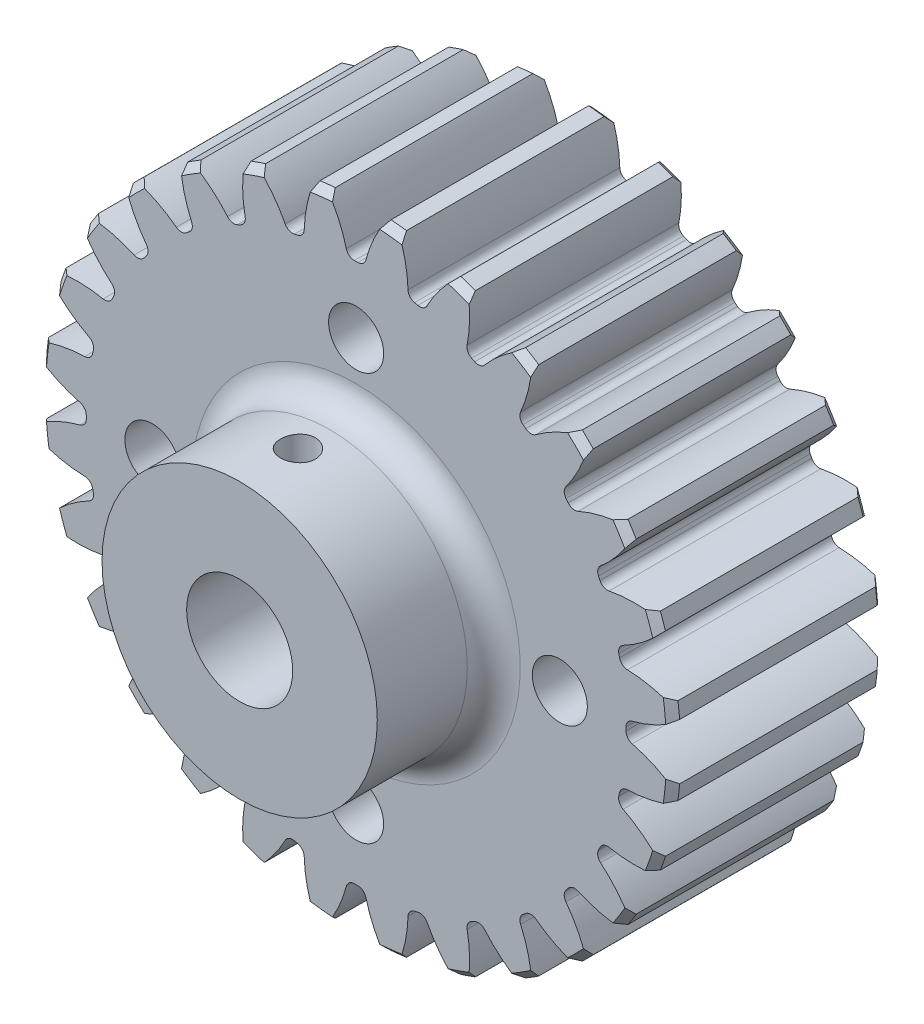
SolidWorks part; units mm, degrees
ref_plane "Front Plane" through (0, 0, 0) normal (0, 0, 1) x (1, 0, 0)
ref_plane "Top Plane" through (0, 0, 0) normal (0, 1, 0) x (1, 0, 0)
ref_plane "Right Plane" through (0, 0, 0) normal (1, 0, 0) x (0, 0, -1)
sketch "Sketch1" plane through (0, 0, 0) normal (0, 0, 1) x (1, 0, 0)
  line L0 (0, 0) -> (0, 28) construction
  line L1 (-8.999, 31.2754) -> (8.999, 24.7246) construction
  circle A0 centre (0, 0) radius 25.5 construction
  circle A1 centre (0, 0) radius 30 construction
  circle A2 centre (0, 0) radius 28 construction
  circle A3 centre (0, 0) radius 26.3114 construction
  circle A4 centre (0, 0) radius 22.5 construction
  circle A5 centre (0, 0) radius 6 construction
  point P8 (1, 0)
  point P13 (14, 0)
  dimension "OD" = 60
  dimension "Root Diameter" = 51
  dimension "Gear Pitch Diameter" = 56
  dimension "Base Diameter" = 52.6228
  dimension "Hub Diameter" = 45
  dimension "For Shaft Diameter" = 12
  dimension "Pressure Angle" = 20
  dimension "Number of Teeth" = 28
  dimension "Module" = 2
sketch "Sketch2" plane through (0, 0, 0) normal (1, 0, 0) x (0, 0, -1)
  line L0 (-16, 0) -> (20, 0) construction
  line L1 (20, 30) -> (20, -30) construction
  line L2 (0, -22.5) -> (-16, -22.5) construction
  line L3 (-16, 30) -> (20, 30) construction
  line L8 (-16, -22.5) -> (-16, 22.5) construction
  point P4 (0, 30)
  point P5 (-8, 0)
  dimension "Overall Width" = 36
  dimension "Hub Width" = 16
  dimension "Approx Set Screw Positon" = 8
  dimension "Face Width" = 20
sketch "Sketch3" plane through (0, 0, 0) normal (0, 0, 1) x (1, 0, 0)
  circle A0 centre (0, 0) radius 30
  circle A1 centre (0, 0) radius 30 construction
extrude "Boss-Extrude1" add sketch "Sketch3" against normal up to vertex (20 mm away) and the other way up to vertex (16 mm away) up to point (0, 0, -20) other way up to point (0, 0, 16)
sketch "Sketch5" plane through (0, 0, 0) normal (1, 0, 0) x (0, 0, -1)
  line L1 (0, 22.5) -> (-16, 22.5)
  line L2 (0, 22.5) -> (0, 30)
  line L3 (0, 30) -> (-16, 30)
  line L4 (-16, 22.5) -> (-16, 30)
  line L5 (-16, 0) -> (20, 0)
  line L6 (-16, 0) -> (-16, 6)
  line L7 (-16, 6) -> (20, 6)
  line L8 (20, 0) -> (20, 6)
  point P5 (0, 22.5)
  point P12 (0, 6)
revolve "Cut-Revolve1" cut sketch "Sketch5" angle 360 about L0
fillet "Fillet2" radius 0.671 1 edges at (0, -22.5, 0)
chamfer "Chamfer1" distance 0.671 angle 45 5 edges at (0, -6, -20) (0, -30, 0) (30, 0, -20) (0, -6, 16) (0, -22.5, 16)
sketch "Sketch4" plane through (0, 0, 0) normal (0, 0, 1) x (1, 0, 0)
  line L0 (25.4879, 0.7854) -> (25.4879, -0.7854)
  arc A3 (29.8844, 2.6316) -> (29.8844, -2.6316) centre (0, 0) cw
  circle A4 centre (0, 0) radius 30 construction
  arc A5 (25.4879, 0.7854) -> (29.8844, 2.6316) centre (22.9219, 13.0538) ccw
  circle A8 centre (0, 0) radius 25.5 construction
  arc A9 (25.4879, -0.7854) -> (29.8844, -2.6316) centre (22.9219, -13.0538) cw
  spline S0 degree 4 poles (26.2891, 1.0836) (26.2949, 1.0839) (26.3112, 1.085) (26.3421, 1.0878) (26.3923, 1.0937) (26.4563, 1.1028) (26.5387, 1.1166) (26.6357, 1.1354) (26.7419, 1.1588) (26.8572, 1.187) (26.972, 1.2177) (27.0862, 1.2508) (27.1997, 1.2858) (27.3368, 1.3307) (27.5008, 1.388) (27.6916, 1.4601) (27.9071, 1.5478) (28.1257, 1.6435) (28.3399, 1.743) (28.5551, 1.8495) (28.7626, 1.9568) (28.9769, 2.0743) (29.174, 2.1859) (29.3935, 2.3177) (29.5702, 2.426) (29.8016, 2.5761) (29.9378, 2.6669) (30.0966, 2.7755) (30.1668, 2.8251) (30.2101, 2.8556) knots 0 0 0 0 0 0.005377 0.015084 0.028532 0.04661 0.064855 0.092111 0.119476 0.146842 0.174209 0.201575 0.228941 0.256307 0.307035 0.361767 0.4165 0.471232 0.525964 0.580697 0.635429 0.690161 0.744894 0.799626 0.854358 0.909091 0.954545 1 1 1 1 1 construction
  spline S1 degree 4 poles (26.2891, 1.0836) (26.2949, 1.0839) (26.3112, 1.085) (26.3421, 1.0878) (26.3923, 1.0937) (26.4563, 1.1028) (26.5387, 1.1166) (26.6357, 1.1354) (26.7419, 1.1588) (26.8572, 1.187) (26.972, 1.2177) (27.0862, 1.2508) (27.1997, 1.2858) (27.3368, 1.3307) (27.5008, 1.388) (27.6916, 1.4601) (27.9071, 1.5478) (28.1257, 1.6435) (28.3399, 1.743) (28.5551, 1.8495) (28.7626, 1.9568) (28.9769, 2.0743) (29.174, 2.1859) (29.3935, 2.3177) (29.5702, 2.426) (29.7514, 2.5436) (29.8394, 2.6016) (29.8844, 2.6316) knots 0 0 0 0 0 0.005377 0.015084 0.028532 0.04661 0.064855 0.092111 0.119476 0.146842 0.174209 0.201575 0.228941 0.256307 0.307035 0.361767 0.4165 0.471232 0.525964 0.580697 0.635429 0.690161 0.744894 0.799626 0.854358 0.909091 0.909091 0.909091 0.909091 0.909091 construction
  spline S2 degree 4 poles (26.2891, -1.0836) (26.2949, -1.0839) (26.3112, -1.085) (26.3421, -1.0878) (26.3923, -1.0937) (26.4563, -1.1028) (26.5387, -1.1166) (26.6357, -1.1354) (26.7419, -1.1588) (26.8572, -1.187) (26.972, -1.2177) (27.0862, -1.2508) (27.1997, -1.2858) (27.3368, -1.3307) (27.5008, -1.388) (27.6916, -1.4601) (27.9071, -1.5478) (28.1257, -1.6435) (28.3399, -1.743) (28.5551, -1.8495) (28.7626, -1.9568) (28.9769, -2.0743) (29.174, -2.1859) (29.3935, -2.3177) (29.5702, -2.426) (29.8016, -2.5761) (29.9378, -2.6669) (30.0966, -2.7755) (30.1668, -2.8251) (30.2101, -2.8556) knots 0 0 0 0 0 0.005377 0.015084 0.028532 0.04661 0.064855 0.092111 0.119476 0.146842 0.174209 0.201575 0.228941 0.256307 0.307035 0.361767 0.4165 0.471232 0.525964 0.580697 0.635429 0.690161 0.744894 0.799626 0.854358 0.909091 0.954545 1 1 1 1 1 construction
  spline S3 degree 4 poles (26.2891, -1.0836) (26.2949, -1.0839) (26.3112, -1.085) (26.3421, -1.0878) (26.3923, -1.0937) (26.4563, -1.1028) (26.5387, -1.1166) (26.6357, -1.1354) (26.7419, -1.1588) (26.8572, -1.187) (26.972, -1.2177) (27.0862, -1.2508) (27.1997, -1.2858) (27.3368, -1.3307) (27.5008, -1.388) (27.6916, -1.4601) (27.9071, -1.5478) (28.1257, -1.6435) (28.3399, -1.743) (28.5551, -1.8495) (28.7626, -1.9568) (28.9769, -2.0743) (29.174, -2.1859) (29.3935, -2.3177) (29.5702, -2.426) (29.7514, -2.5436) (29.8394, -2.6016) (29.8844, -2.6316) knots 0 0 0 0 0 0.005377 0.015084 0.028532 0.04661 0.064855 0.092111 0.119476 0.146842 0.174209 0.201575 0.228941 0.256307 0.307035 0.361767 0.4165 0.471232 0.525964 0.580697 0.635429 0.690161 0.744894 0.799626 0.854358 0.909091 0.909091 0.909091 0.909091 0.909091 construction
  dimension "D1" = 1.5708
extrude "Cut-Extrude1" cut sketch "Sketch4" against normal through all both and the other way through all
fillet "Fillet1" radius 0.7854 2 edges at (25.4879, 0.7854, -10) (25.4879, -0.7854, -10)
pattern_circular "CirPattern1" count 28 over 360 about axis through (0, 0, 16) along (0, 0, -1) of "Cut-Extrude1", "Fillet1"
sketch "Sketch6" plane through (0, 0, -20) normal (0, 0, -1) x (-1, 0, 0)
  circle A0 centre (0, 0) radius 6.671
  circle A1 centre (0, 0) radius 5.0075
  circle A2 centre (0, 0) radius 6.671 construction
  dimension "D1" = 10.015
extrude "Boss-Extrude2" add sketch "Sketch6" against normal through all
sketch "Sketch7" plane through (0, 0, 16) normal (0, 0, 1) x (1, 0, 0)
  circle A0 centre (0, 0) radius 23.171
  circle A2 centre (0, 0) radius 13
  circle A3 centre (0, 0) radius 23.171 construction
  circle M3 centre (0, 0) radius 5.0075
  dimension "D1" = 26
extrude "Cut-Extrude2" cut sketch "Sketch7" against normal up to surface (16 mm away) up to face at (0, 0, 0)
sketch "Sketch8" plane through (0, 0, 0) normal (0, 0, 1) x (1, 0, 0)
  circle A0 centre (0, 19.24) radius 2.6
  circle A1 centre (0, 0) radius 5.0075 construction
  circle A4 centre (19.24, 0) radius 2.6
  circle A5 centre (0, -19.24) radius 2.6
  circle A6 centre (-19.24, 0) radius 2.6
  point P18 (0, 0)
  dimension "D1" = 5.2
  dimension "D3" = 19.24
  dimension "D2" = 4
extrude "Cut-Extrude3" cut sketch "Sketch8" against normal through all
extrude "Cut-Extrude4" cut sketch "Sketch7<2>" against normal blind 5 contours A2 M3 region at (-12.6323, 0, 16)
sketch "Sketch7<2>" plane through (0, 0, 16) normal (0, 0, 1) x (1, 0, 0) same geometry as "Sketch7"
sketch "Sketch9" plane through (0, 0, 0) normal (0, 1, 0) x (1, 0, 0)
  line L0 (0, 0) -> (0, -11) construction
  line L1 (-13, 0) -> (13, 0) construction
  line L2 (-13, -11) -> (13, -11) construction
  circle A0 centre (0, -5.5) radius 2.25
  circle A1 centre (0, -5.5) radius 2.8
  dimension "D1" = 5.6
  dimension "D2" = 4.5
fillet "Fillet3" radius 2.5 1 edges at (0, -13, 0)
sketch "Sketch10" plane through (0, 0, 0) normal (0, 1, 0) x (1, 0, 0)
  point P0 (0, -5.5)
hole_wizard "M4x0.7 Tapped Hole1" positions "Sketch10" profile "Sketch12" tap size "M4x0.7" standard "ANSI Metric" end condition through all
sketch "Sketch12" plane through (0, 0, 5.5) normal (1, 0, 0) x (0, 0, -1)
  line L0 (0, 0) -> (0, 29.8844)
  line L1 (0, 29.8844) -> (1.65, 29.8844)
  line L2 (1.65, 29.8844) -> (1.65, 0)
  line L5 (1.65, 0) -> (0, 0)
  line L11 (0, -6.35) -> (0, 107.95) construction
  dimension "Thru Tap Drill Dia." = 3.3
  dimension "Thru Tap Drill Depth" = 29.8844
cosmetic thread "Hole Thread1" parameters "D2"=4
equation "\"Number of Teeth\"= 28"
equation "\"Module\"= 2"
equation "\"Diametral Pitch\"= 1 / \"Module\""
equation "\"Dedendum\"= 1.25 / \"Diametral Pitch\""
equation "\"Pitch Diameter\"= \"Module\" * \"Number of Teeth\""
equation "\"Root Diameter\"= \"Pitch Diameter\" - ( 2 * \"Dedendum\" )"
equation "\"Root Diameter@Sketch1\"=\"Root Diameter\""
equation "\"OD@Sketch1\" = \"Outside Diameter\""
equation "\"D1@CirPattern1\"=\"Number of Teeth\""
equation "\"Pressure Angle\"=20"
equation "\"Base Diameter\"= \"Pitch Diameter\" * cos ( \"Pressure Angle\" )"
equation "\"Outside Diameter\"= ( \"Number of Teeth\" + 2 ) / \"Diametral Pitch\""
equation "\"Pitch Angle\"= 360deg / \"Number of Teeth\""
equation "\"Alpha\"= sqr ( \"Pitch Diameter\" ^ 2 - \"Base Diameter\" ^ 2 ) / \"Base Diameter\" * 180 / PI - \"Pressure Angle\""
equation "\"Beta\"= ( \"Pitch Angle\" / 4 - \"Alpha\" )"
equation "\"Phi\"= sqr ( ( \"Outside Diameter\" / 2 ) ^ 2 - ( \"Base Diameter\" / 2 ) ^ 2 ) / ( \"Base Diameter\" / 2 )"
equation "\"Addendum\"= 1 / \"Diametral Pitch\""
equation "\"WorkingDepth\"= 2 / \"Diametral Pitch\""
equation "\"WholeDepth\"= 2.25 / \"Diametral Pitch\""
equation "\"Clearance\"= 0.25 / \"Diametral Pitch\""
equation "\"ToothThickness\"= ( pi * 2 ) / \"Diametral Pitch\""
equation "\"CircularPitch\"= pi / \"Diametral Pitch\""
equation "\"Number of Teeth@Sketch1\"=\"Number of Teeth\""
equation "\"Module@Sketch1\"=\"Module\""
equation "\"Pressure Angle@Sketch1\"=\"Pressure Angle\""
equation "\"Gear Pitch Diameter@Sketch1\"=\"Pitch Diameter\""
equation "\"Base Diameter@Sketch1\"=\"Base Diameter\""
equation "\"Fillet\"= \"Clearance\" * cos ( \"Pressure Angle\" ) * tan ( ( 90 + \"Pressure Angle\" ) / 2 )"
equation "\"D1@Fillet2\"=\"Fillet\""
equation "\"Approx Set Screw Positon@Sketch2\" = \"Hub Width@Sketch2\" / 2"
equation "\"D2\"= \"Fillet\" * 2"
equation "\"D1@Chamfer1\"=\"Fillet\""
equation "\"D1@Sketch4\"=\"CircularPitch\"*0.25"
equation "\"D1@Fillet1\"=\"CircularPitch\"*0.125"
